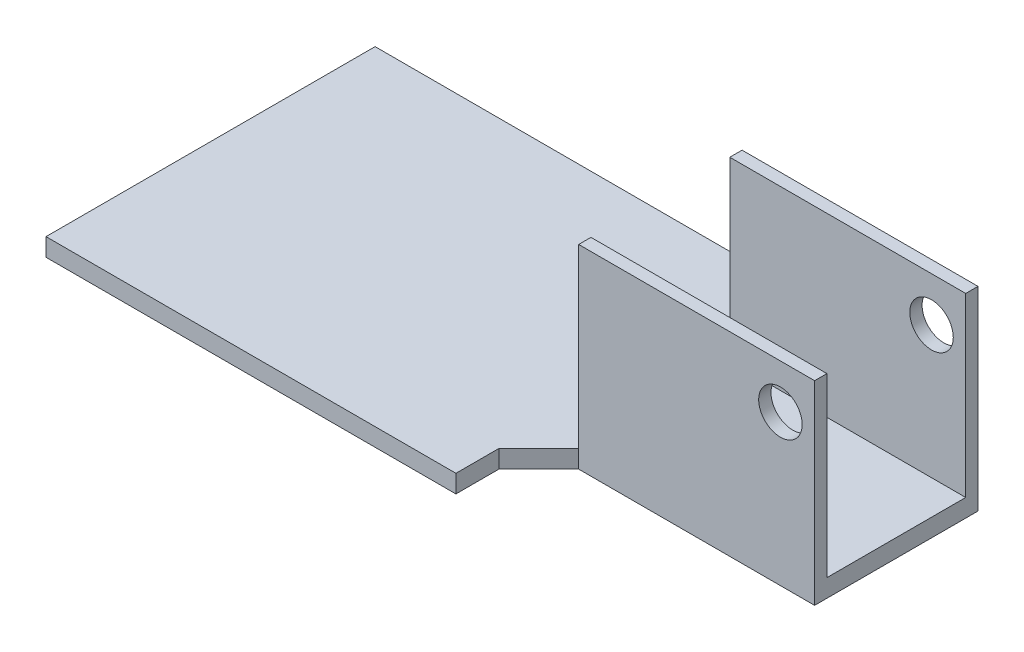
SolidWorks part; units mm, degrees
ref_plane "Front Plane" through (0, 0, 0) normal (0, 0, 1) x (1, 0, 0)
ref_plane "Top Plane" through (0, 0, 0) normal (0, 1, 0) x (1, 0, 0)
ref_plane "Right Plane" through (0, 0, 0) normal (1, 0, 0) x (0, 0, -1)
sketch "Sketch8" plane through (0, 0, 0) normal (0, 1, 0) x (1, 0, 0)
  line L0 (-44.9741, -2.9009) -> (-44.9741, -40.7469)
  line L1 (-44.9741, -40.7469) -> (2.1658, -40.7469)
  line L2 (2.1658, -40.7469) -> (2.1658, -35.808)
  line L3 (2.1658, -2.9009) -> (-44.9741, -2.9009)
  line L4 (2.1658, -7.8398) -> (6.7556, -12.4295)
  line L5 (2.1658, -7.8398) -> (2.1658, -2.9009)
  line L6 (6.7556, -31.2182) -> (2.1658, -35.808)
  line L7 (6.7556, -12.4295) -> (33.8879, -12.4295)
  line L8 (33.8879, -12.4295) -> (33.8879, -31.2182)
  line L9 (33.8879, -31.2182) -> (6.7556, -31.2182)
  line L10 (-44.9741, -21.8239) -> (33.8879, -21.8239) construction
  dimension "D1" = 37.846
  dimension "D2" = 47.1399
  dimension "D3" = 45
  dimension "D4" = 45
  dimension "D5" = 4.5898
  dimension "D6" = 18.923
  dimension "D7" = 4.9389
  dimension "D8" = 78.8619
extrude "Boss-Extrude6" add sketch "Sketch8" along normal blind 2.0599
sketch "Sketch9" plane through (0, 2.0599, 0) normal (0, 1, 0) x (1, 0, 0)
  line L0 (33.8879, -13.8418) -> (6.7556, -13.8418)
  line L1 (33.8879, -31.2182) -> (33.8879, -12.4295) construction
  line L2 (6.7556, -13.8418) -> (6.7556, -12.4295)
  line L3 (6.7556, -12.4295) -> (33.8879, -12.4295)
  line L4 (33.8879, -12.4295) -> (33.8879, -13.8418)
  line L5 (6.7556, -31.2182) -> (6.7556, -29.806)
  line L6 (6.7556, -29.806) -> (33.8879, -29.806)
  line L7 (33.8879, -29.806) -> (33.8879, -31.2182)
  line L8 (33.8879, -31.2182) -> (6.7556, -31.2182)
  dimension "D1" = 1.4122
  dimension "D2" = 1.4122
extrude "Boss-Extrude7" add sketch "Sketch9" along normal blind 20.32
sketch "Sketch10" plane through (0, 0, 31.2182) normal (0, 0, 1) x (1, 0, 0)
  line L0 (6.7556, 0) -> (33.8879, 0) construction
  line L1 (-44.9741, 2.0599) -> (-44.9741, 0) construction
  circle A0 centre (29.9559, 17.2847) radius 2.5006
  dimension "D2" = 74.93
  dimension "D1" = 17.2847
extrude "Cut-Extrude3" cut sketch "Sketch10" against normal blind 25.4
sketch "Sketch11" plane through (0, 0, 13.8418) normal (0, 0, 1) x (1, 0, 0)
  line L0 (6.7556, 18.3467) -> (23.4683, 8.6976)
  line L1 (6.7556, 22.3799) -> (6.7556, 2.0599) construction
  line L2 (23.4683, 8.6976) -> (23.4683, 0)
  line L3 (6.7556, 0) -> (33.8879, 0) construction
  dimension "D1" = 60
